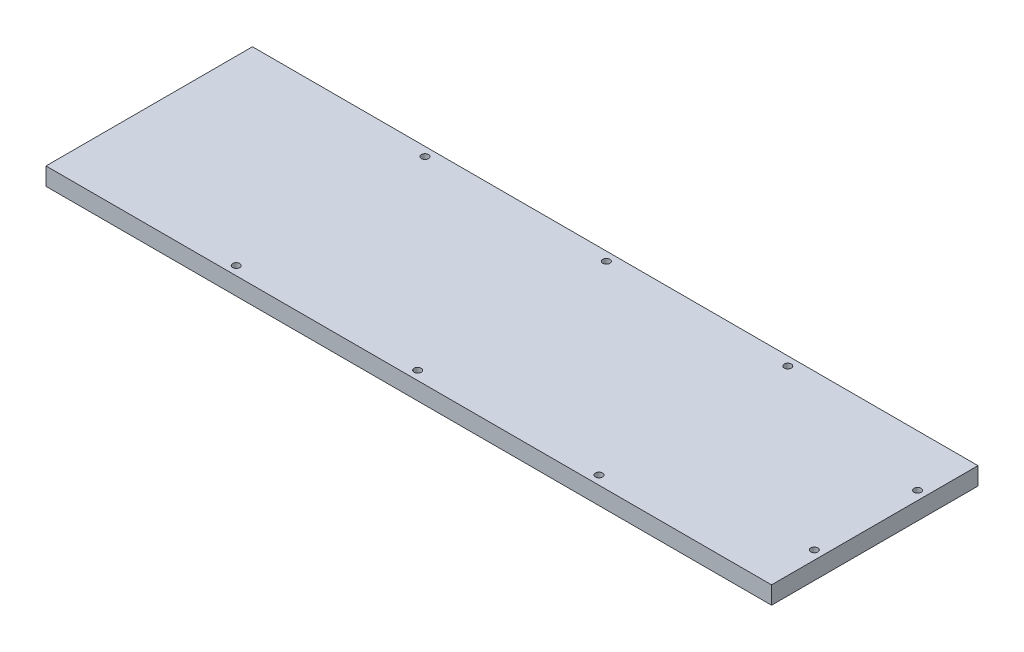
SolidWorks part; units mm, degrees
ref_plane "前视基准面" through (0, 0, 0) normal (0, 0, 1) x (1, 0, 0)
ref_plane "上视基准面" through (0, 0, 0) normal (0, 1, 0) x (1, 0, 0)
ref_plane "右视基准面" through (0, 0, 0) normal (1, 0, 0) x (0, 0, -1)
other "Configuration Table"
sketch "草图1" plane through (0, 0, 0) normal (0, 1, 0) x (1, 0, 0)
  line L1 (-61.5, -17.5) -> (61.5, -17.5)
  line L2 (-61.5, -17.5) -> (-61.5, 17.5)
  line L3 (-61.5, 17.5) -> (61.5, 17.5)
  line L4 (61.5, -17.5) -> (61.5, 17.5)
  line L5 (-61.5, -17.5) -> (61.5, 17.5) construction
  line L6 (-61.5, 17.5) -> (61.5, -17.5) construction
  point P0 (0, 0)
  dimension "D1" = 123
  dimension "D5" = 35
extrude "凸台-拉伸1" add sketch "草图1" along normal blind 3 contours L3 L4 L1 L2
sketch "草图2" plane through (0, 0, 0) normal (0, -1, 0) x (1, 0, 0)
  line L0 (-61.5, 16) -> (-30.75, 16) construction
  line L1 (-61.5, 17.5) -> (-61.5, -17.5) construction
  line L2 (-30.75, 16) -> (0, 16) construction
  line L3 (0, 16) -> (30.75, 16) construction
  line L4 (30.75, 16) -> (61.5, 16) construction
  line L5 (61.5, 17.5) -> (61.5, -17.5) construction
  line L6 (-61.5, -16) -> (-30.75, -16) construction
  line L7 (-30.75, -16) -> (0, -16) construction
  line L8 (0, -16) -> (30.75, -16) construction
  line L9 (30.75, -16) -> (61.5, -16) construction
  line L10 (60, 17.5) -> (60, 8.75) construction
  line L11 (-61.5, 17.5) -> (61.5, 17.5) construction
  line L12 (60, 8.75) -> (60, 0) construction
  line L13 (60, 0) -> (60, -8.75) construction
  line L14 (60, -8.75) -> (60, -17.5) construction
  line L15 (-61.5, -17.5) -> (61.5, -17.5) construction
  circle A0 centre (-30.75, 16) radius 0.6
  circle A1 centre (-30.75, 16) radius 1
  circle A2 centre (30.75, 16) radius 0.6
  circle A3 centre (30.75, 16) radius 1
  circle A4 centre (-30.75, -16) radius 0.6
  circle A5 centre (-30.75, -16) radius 1
  circle A6 centre (30.75, -16) radius 0.6
  circle A7 centre (30.75, -16) radius 1
  circle A8 centre (0, 16) radius 1
  circle A9 centre (0, 16) radius 0.6
  circle A10 centre (0, -16) radius 1
  circle A11 centre (0, -16) radius 0.6
  circle A12 centre (60, 8.75) radius 0.6
  circle A13 centre (60, 8.75) radius 1
  circle A14 centre (60, -8.75) radius 1
  circle A15 centre (60, -8.75) radius 0.6
  dimension "D1" = 1.2
  dimension "D2" = 2
  dimension "D3" = 1.5
  dimension "D4" = 1.5
  dimension "D5" = 1.5
extrude "切除-拉伸1" cut sketch "草图2" against normal through all contours A4 | A11 | A6 | A15 | A12 | A2 | A9 | A0
extrude "切除-拉伸2" cut sketch "草图2<3>" against normal blind 1.5 contours A1 | A8 | A3 | A13 | A14 | A7 | A10 | A5
sketch "草图2<3>" plane through (0, 0, 0) normal (0, -1, 0) x (1, 0, 0) same geometry as "草图2"
sketch "草图3" plane through (0, 0, 0) normal (0, -1, 0) x (1, 0, 0)
  line L0 (60, -13) -> (57, -13)
  line L2 (60, -13) -> (60, -16)
  line L3 (60, -16) -> (57, -16)
  line L4 (57, -13) -> (57, -16)
  line L5 (-61.5, 17.5) -> (61.5, 17.5) construction
  line L6 (61.5, 14.5) -> (36.9, 14.5) construction
  line L7 (61.5, 17.5) -> (61.5, -17.5) construction
  line L8 (36.9, 14.5) -> (12.3, 14.5) construction
  line L9 (12.3, 14.5) -> (-12.3, 14.5) construction
  line L10 (-12.3, 14.5) -> (-36.9, 14.5) construction
  line L11 (-36.9, 14.5) -> (-61.5, 14.5) construction
  line L13 (-61.5, 17.5) -> (-61.5, -17.5) construction
  line L14 (60, -13) -> (57, -16) construction
  line L19 (60, -16) -> (57, -13) construction
  line L20 (60, 16) -> (57, 16)
  line L21 (60, 1.5) -> (57, 1.5)
  line L22 (60, 1.5) -> (60, -1.5)
  line L23 (60, -1.5) -> (57, -1.5)
  line L24 (57, 1.5) -> (57, -1.5)
  line L25 (60, 1.5) -> (57, -1.5) construction
  line L26 (60, -1.5) -> (57, 1.5) construction
  line L31 (60, 16) -> (60, 13)
  line L32 (60, 13) -> (57, 13)
  line L33 (38.4, 16) -> (35.4, 16)
  line L34 (38.4, 16) -> (38.4, 13)
  line L35 (38.4, 13) -> (35.4, 13)
  line L36 (35.4, 16) -> (35.4, 13)
  line L37 (38.4, 16) -> (35.4, 13) construction
  line L38 (38.4, 13) -> (35.4, 16) construction
  line L39 (13.8, 16) -> (10.8, 16)
  line L40 (13.8, 16) -> (13.8, 13)
  line L41 (13.8, 13) -> (10.8, 13)
  line L42 (10.8, 16) -> (10.8, 13)
  line L43 (13.8, 16) -> (10.8, 13) construction
  line L44 (13.8, 13) -> (10.8, 16) construction
  line L49 (57, 16) -> (57, 13)
  line L50 (60, 16) -> (57, 13) construction
  line L51 (-10.8, 16) -> (-13.8, 16)
  line L52 (-10.8, 16) -> (-10.8, 13)
  line L53 (-10.8, 13) -> (-13.8, 13)
  line L54 (-13.8, 16) -> (-13.8, 13)
  line L55 (-10.8, 16) -> (-13.8, 13) construction
  line L56 (-10.8, 13) -> (-13.8, 16) construction
  line L57 (-35.4, 16) -> (-38.4, 16)
  line L58 (-35.4, 16) -> (-35.4, 13)
  line L59 (-35.4, 13) -> (-38.4, 13)
  line L60 (-38.4, 16) -> (-38.4, 13)
  line L61 (-35.4, 16) -> (-38.4, 13) construction
  line L62 (-35.4, 13) -> (-38.4, 16) construction
  line L63 (60, 13) -> (57, 16) construction
  line L64 (58.5, -14.5) -> (58.5, 0) construction
  line L65 (58.5, 0) -> (58.5, 14.5) construction
  line L70 (38.4, -13) -> (35.4, -13)
  line L71 (38.4, -13) -> (38.4, -16)
  line L72 (38.3969, -94.4467) -> (35.3969, -94.4467)
  line L73 (38.3969, -94.4467) -> (38.3969, -97.4467)
  line L74 (38.3969, -97.4467) -> (35.3969, -97.4467)
  line L75 (35.3969, -94.4467) -> (35.3969, -97.4467)
  line L76 (38.3969, -94.4467) -> (35.3969, -97.4467) construction
  line L77 (38.3969, -97.4467) -> (35.3969, -94.4467) construction
  line L78 (38.4, -16) -> (35.4, -16)
  line L79 (35.4, -13) -> (35.4, -16)
  line L80 (38.4, -13) -> (35.4, -16) construction
  line L81 (38.4, -16) -> (35.4, -13) construction
  line L82 (13.8, -13) -> (10.8, -13)
  line L83 (13.8, -13) -> (13.8, -16)
  line L84 (13.8, -16) -> (10.8, -16)
  line L85 (10.8, -13) -> (10.8, -16)
  line L86 (13.8, -13) -> (10.8, -16) construction
  line L87 (13.8, -16) -> (10.8, -13) construction
  line L88 (-10.8, -13) -> (-13.8, -13)
  line L89 (-10.8, -13) -> (-10.8, -16)
  line L90 (-10.8, -16) -> (-13.8, -16)
  line L91 (-13.8, -13) -> (-13.8, -16)
  line L92 (-10.8, -13) -> (-13.8, -16) construction
  line L93 (-10.8, -16) -> (-13.8, -13) construction
  line L94 (-35.4, -13) -> (-38.4, -13)
  line L95 (-35.4, -13) -> (-35.4, -16)
  line L96 (-35.4, -16) -> (-38.4, -16)
  line L97 (-38.4, -13) -> (-38.4, -16)
  line L98 (-35.4, -13) -> (-38.4, -16) construction
  line L99 (-35.4, -16) -> (-38.4, -13) construction
  line L100 (58.5, -14.5) -> (36.9, -14.5) construction
  line L101 (36.9, -14.5) -> (12.3, -14.5) construction
  line L102 (12.3, -14.5) -> (-12.3, -14.5) construction
  line L103 (-12.3, -14.5) -> (-36.9, -14.5) construction
  point P23 (61.5, 0)
  point P27 (36.9, -14.5)
  point P68 (12.3, -14.5)
  point P69 (-12.3, -14.5)
  point P70 (-36.9, -14.5)
  dimension "D1" = 3
  dimension "D2" = 3
  dimension "D3" = 3
  dimension "D4" = 3
extrude "切除-拉伸3" cut sketch "草图3" against normal blind 2
